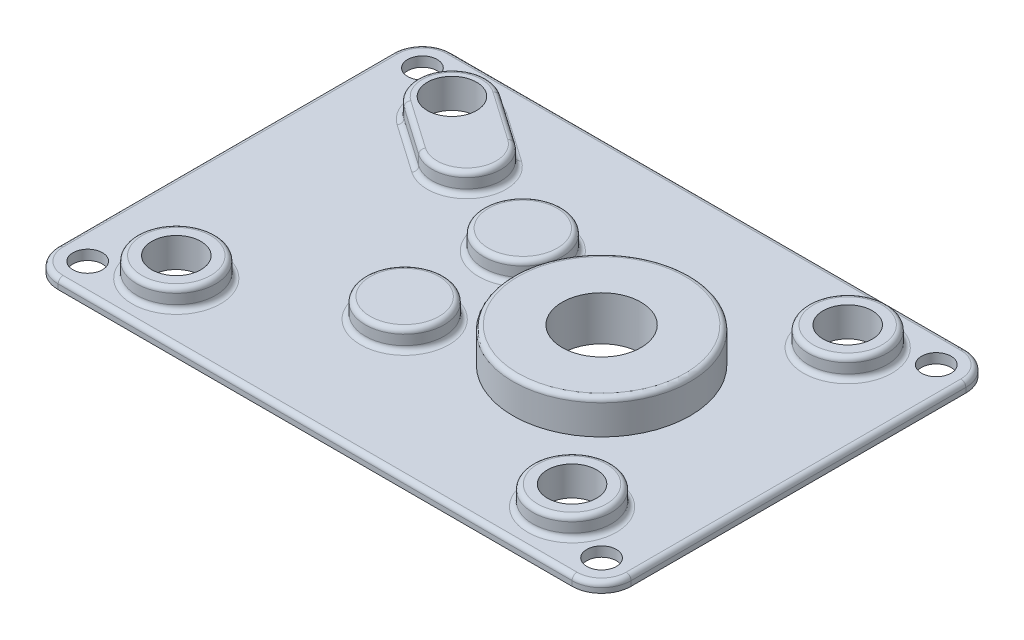
SolidWorks part; units mm, degrees
material "1.0037 (S235JR)"
ref_plane "Front" through (0, 0, 0) normal (0, 0, 1) x (1, 0, 0)
ref_plane "Top" through (0, 0, 0) normal (0, 1, 0) x (1, 0, 0)
ref_plane "Right" through (0, 0, 0) normal (1, 0, 0) x (0, 0, -1)
sketch "Sketch1" plane through (0, 0, 0) normal (0, 1, 0) x (1, 0, 0)
  line L1 (-26.1, 20) -> (26.1, 20)
  line L2 (-29.1, 17) -> (-29.1, -17)
  line L3 (-26.1, -20) -> (26.1, -20)
  line L4 (29.1, 17) -> (29.1, -17)
  line L5 (-29.1, 20) -> (29.1, -20) construction
  line L6 (-29.1, -20) -> (29.1, 20) construction
  arc A0 (-26.1, 20) -> (-29.1, 17) centre (-26.1, 17) ccw
  arc A1 (-29.1, -17) -> (-26.1, -20) centre (-26.1, -17) ccw
  arc A2 (26.1, -20) -> (29.1, -17) centre (26.1, -17) ccw
  arc A3 (26.1, 20) -> (29.1, 17) centre (26.1, 17) cw
  point P0 (0, 0)
  dimension "D3" = 3
  dimension "D1" = 40
  dimension "D2" = 58.2
extrude "Boss-Extrude1" add sketch "Sketch1" along normal blind 1
sketch "Sketch2" plane through (0, 1, 0) normal (0, 1, 0) x (1, 0, 0)
  line L0 (0, 22.1659) -> (0, -26.1295) construction
  line L1 (29.1, -17) -> (29.1, 17) construction
  line L3 (-33.9044, 0) -> (36.8314, 0) construction
  line L4 (-20.1, 14) -> (20.1, -14) construction
  line L5 (-18.0996, 16.872) -> (-13.1762, 13.4427)
  line L6 (-17.177, 7.6987) -> (-22.1004, 11.128)
  circle A0 centre (20.1, -14) radius 4
  circle A1 centre (20.1, -14) radius 2.5
  circle A2 centre (20.1, 14) radius 2.5
  circle A3 centre (20.1, 14) radius 4
  circle A4 centre (-20.1, -14) radius 2.5
  circle A5 centre (-20.1, -14) radius 4
  circle A6 centre (-20.1, 14) radius 2.5
  arc A7 (-18.0996, 16.872) -> (-22.1004, 11.128) centre (-20.1, 14) ccw
  arc A8 (-17.177, 7.6987) -> (-13.1762, 13.4427) centre (-15.1766, 10.5707) ccw
  circle A9 centre (-4.9, -6) radius 4
  circle A10 centre (-4.9, 6) radius 4
  circle A11 centre (-26.1, -17) radius 1.5
  arc A12 (-29.1, -17) -> (-26.1, -20) centre (-26.1, -17) ccw construction
  circle A13 centre (-26.1, 17) radius 1.5
  circle A14 centre (26.1, 17) radius 1.5
  circle A15 centre (26.1, -17) radius 1.5
  dimension "D2" = 5
  dimension "D3" = 8
  dimension "D5" = 1
  dimension "D6" = 13
  dimension "D7" = 8
  dimension "D10" = 3
  dimension "D1" = 9
  dimension "D4" = 28
  dimension "D8" = 12
  dimension "D9" = 34
extrude "Cut-Extrude3" cut sketch "Sketch2" against normal blind 2 contours A15 | A14 | A11 | A13 | A2 | A6 | A4 | A1 region at (-26.1, 1, 17) region at (-26.1, 1, -17) region at (26.1, 1, -17) region at (26.1, 1, 17)
extrude "Boss-Extrude3" add sketch "Sketch2<6>" along normal blind 2 contours A3 A2 | A0 A1 | A5 A4 | L6 A8 L5 A7 A6 | A9 | A10 region at (-16.8439, 1, -11.7321) region at (16.2131, 1, 14) region at (16.2131, 1, -14) region at (-23.9869, 1, 14) region at (-4.9, 1, 6) region at (-4.9, 1, -6)
sketch "Sketch2<6>" plane through (0, 1, 0) normal (0, 1, 0) x (1, 0, 0) same geometry as "Sketch2"
fillet "Fillet1" radius 0.5 17 edges at (-28.2213, 1, 19.1213) (-29.1, 1, 0) (-28.2213, 1, -19.1213) (0, 1, -20) (28.2213, 1, -19.1213) (29.1, 1, 0) (28.2213, 1, 19.1213) (0, 1, 20) (-12.3046, 3, -8.5703) (-15.6379, 3, -15.1574) (-22.972, 3, -16.0004) (20.1, 3, -10) (-19.6387, 3, -9.4134) (-4.9, 3, -2) (-4.9, 3, 10) (-20.1, 3, 18) (20.1, 3, 18)
sketch "Sketch3" plane through (0, 1, 0) normal (0, 1, 0) x (1, 0, 0)
  line L0 (29.1, 17) -> (29.1, -17) construction
  circle A0 centre (9.1, 0) radius 4
  circle A1 centre (9.1, 0) radius 9
  dimension "D2" = 8
  dimension "D3" = 5
  dimension "D1" = 20
extrude "Cut-Extrude4" cut sketch "Sketch3" against normal blind 2 contours A0
extrude "Boss-Extrude4" add sketch "Sketch3<3>" along normal blind 3.5
sketch "Sketch3<3>" plane through (0, 1, 0) normal (0, 1, 0) x (1, 0, 0) same geometry as "Sketch3"
fillet "Fillet2" radius 0.5 1 edges at (9.1, 4.5, 9)
fillet "Fillet3" radius 0.5 9 edges at (-12.3046, 1, -8.5703) (-15.6379, 1, -15.1574) (-22.972, 1, -16.0004) (-20.1, 1, 18) (-19.6387, 1, -9.4134) (20.1, 1, -10) (20.1, 1, 18) (-4.9, 1, -2) (-4.9, 1, 10)
